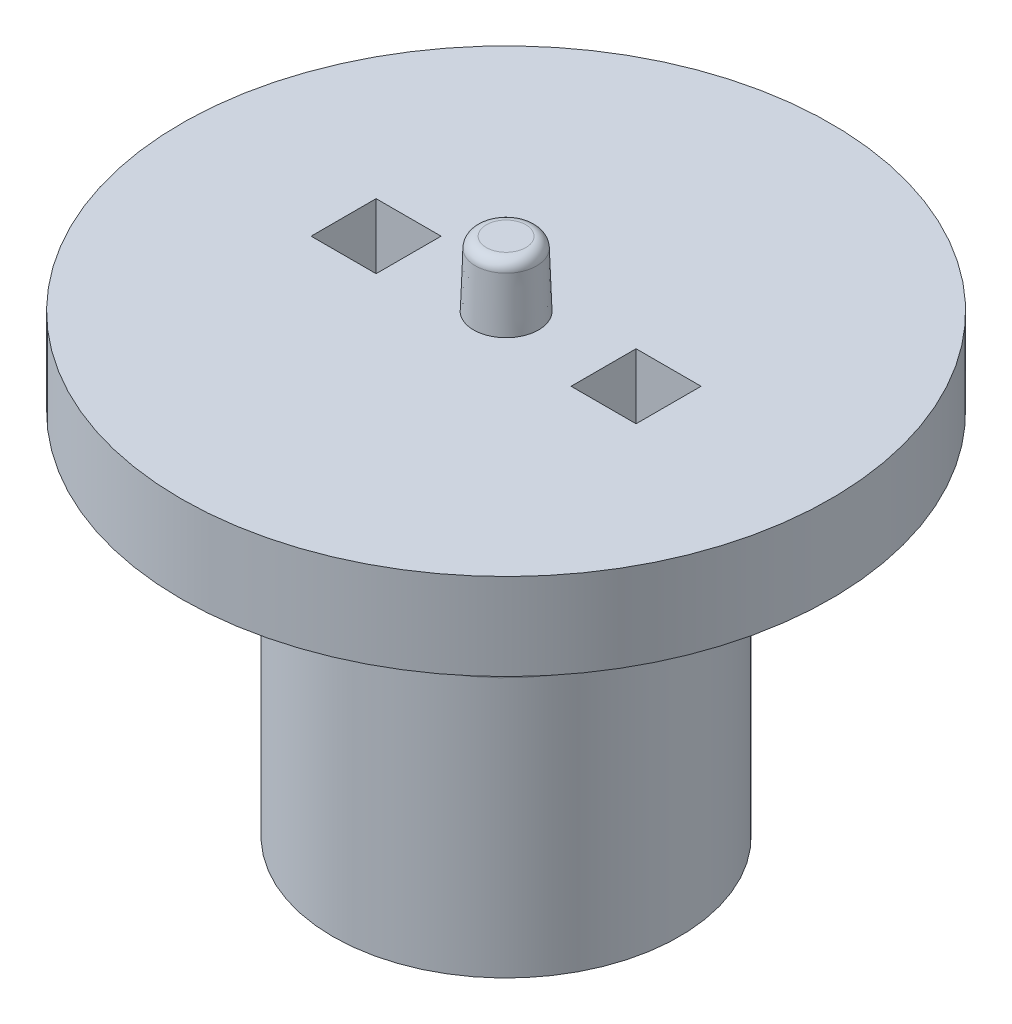
SolidWorks part; units mm, degrees
ref_plane "Front Plane" through (0, 0, 0) normal (0, 0, 1) x (1, 0, 0)
ref_plane "Top Plane" through (0, 0, 0) normal (0, 1, 0) x (1, 0, 0)
ref_plane "Right Plane" through (0, 0, 0) normal (1, 0, 0) x (0, 0, -1)
sketch "Sketch1" plane through (0, 0, 0) normal (0, 1, 0) x (1, 0, 0)
  circle A0 centre (0, 0) radius 8
  circle A1 centre (0, 0) radius 2.575
  dimension "D1" = 16
  dimension "D2" = 5.15
extrude "Boss-Extrude1" add sketch "Sketch1" along normal blind 15
sketch "Sketch2" plane through (0, 0, 0) normal (0, 0, 1) x (1, 0, 0)
  line L1 (0, 7.5) -> (0, 15) construction
  line L2 (0, 7.5) -> (0, 0) construction
  circle A0 centre (0, 7.5) radius 1.25
  dimension "D1" = 2.5
extrude "Cut-Extrude1" cut sketch "Sketch2" against normal through all contours A0
ref_plane "Plane1" through (0, 0, -8) normal (0, 0, -1) x (-1, 0, 0)
sketch "Sketch12" plane through (0, 15, 0) normal (0, 1, 0) x (1, 0, 0)
  circle A0 centre (0, 0) radius 8
  circle A1 centre (0, 0) radius 8 construction
extrude "Boss-Extrude3" add sketch "Sketch12" along normal blind 2
sketch "Sketch10" plane through (0, 17, 0) normal (0, 1, 0) x (1, 0, 0)
  circle A0 centre (0, 0) radius 7.5
sketch "Sketch11" plane through (0, 17, 0) normal (0, 1, 0) x (1, 0, 0)
  line L0 (6, 0) -> (0, 0) construction
  line L1 (-7.5, 1.5) -> (-4.5, 1.5)
  line L2 (-7.5, 1.5) -> (-7.5, -1.5)
  line L3 (-7.5, -1.5) -> (-4.5, -1.5)
  line L4 (-4.5, 1.5) -> (-4.5, -1.5)
  line L5 (-7.5, 1.5) -> (-4.5, -1.5) construction
  line L6 (-7.5, -1.5) -> (-4.5, 1.5) construction
  line L7 (4.5, 1.5) -> (7.5, 1.5)
  line L8 (4.5, 1.5) -> (4.5, -1.5)
  line L9 (4.5, -1.5) -> (7.5, -1.5)
  line L10 (7.5, 1.5) -> (7.5, -1.5)
  line L11 (4.5, 1.5) -> (7.5, -1.5) construction
  line L12 (4.5, -1.5) -> (7.5, 1.5) construction
  line L13 (0, 0) -> (-6, 0) construction
  circle A0 centre (0, 0) radius 15
  point P0 (-6, 0)
  point P5 (6, 0)
  dimension "D4" = 30
  dimension "D1" = 3
  dimension "D2" = 3
  dimension "D3" = 6
  dimension "D5" = 3
extrude "Boss-Extrude2" add sketch "Sketch11" along normal blind 4
sketch "Sketch13" plane through (0, 21, 0) normal (0, 1, 0) x (1, 0, 0)
  circle A0 centre (0, 0) radius 1.5
  dimension "D1" = 3
extrude "Boss-Extrude4" add sketch "Sketch13" along normal blind 3 draft 2
fillet "Fillet2" radius 0.5 1 edges at (0, 24, 1.3952)
fillet "Fillet4" radius 5 1 edges at (0, 17, 8)
